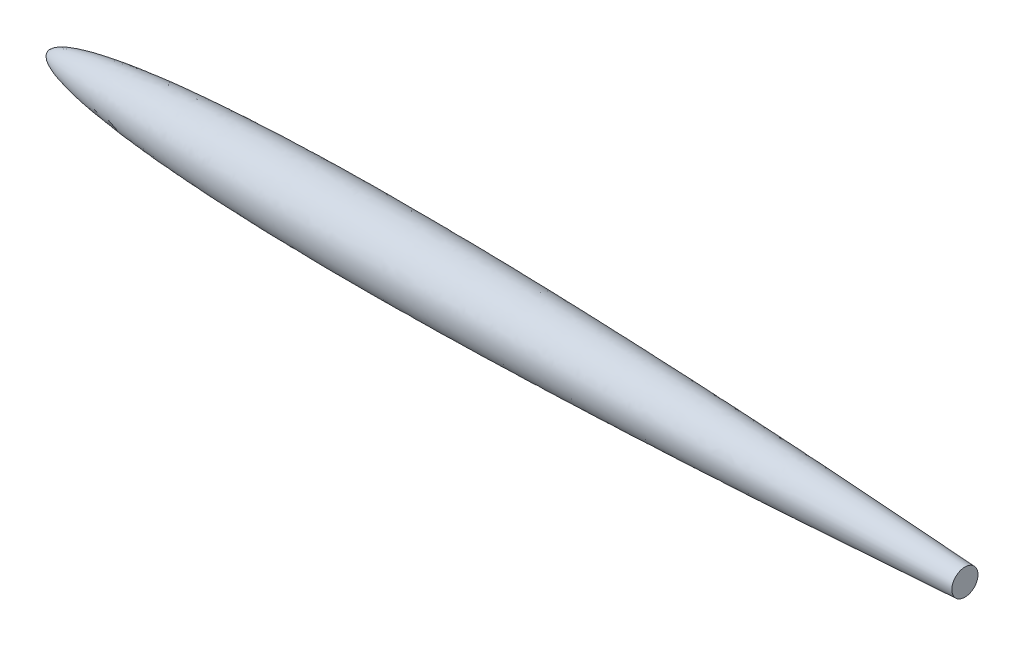
SolidWorks part; units mm, degrees
ref_plane "Front Plane" through (0, 0, 0) normal (0, 0, 1) x (1, 0, 0)
ref_plane "Top Plane" through (0, 0, 0) normal (0, 1, 0) x (1, 0, 0)
ref_plane "Right Plane" through (0, 0, 0) normal (1, 0, 0) x (0, 0, -1)
sketch "Sketch2" plane through (0, 0, 0) normal (0, 1, 0) x (1, 0, 0)
  line L0 (0, 0) -> (11000, 0)
  spline S0 degree 4 poles (0, 0) (0.0002, 1.4166) (0.1225, 4.2408) (0.6739, 8.4547) (2.1097, 13.9385) (4.13, 19.1147) (6.6109, 23.9643) (9.9914, 29.3681) (13.8074, 34.3715) (18.0051, 39.0824) (24.0066, 45.0125) (32.3839, 52.2354) (43.384, 60.1944) (57.0761, 68.6181) (73.983, 77.7243) (92.7893, 86.6435) (113.9578, 95.5167) (137.4556, 104.3111) (166.2995, 114.136) (201.291, 124.8338) (243.0702, 136.2047) (291.673, 147.964) (341.2433, 158.778) (390.608, 168.603) (439.7192, 177.609) (500.6517, 187.9807) (573.4692, 199.2826) (658.6122, 211.1866) (758.0842, 223.6079) (859.6848, 234.9957) (963.387, 245.4645) (1069.1706, 255.1028) (1175.0326, 263.8354) (1280.9578, 271.7615) (1386.9346, 278.9616) (1492.954, 285.5022) (1625.577, 292.9263) (1784.8272, 300.7239) (1970.7211, 308.3762) (2183.2661, 315.3874) (2395.8558, 320.8604) (2608.4762, 324.9557) (2821.1167, 327.8069) (3033.7692, 329.5269) (3299.5919, 330.3841) (3618.5808, 329.5138) (3990.7204, 326.0523) (4415.9852, 319.2091) (4841.2016, 309.8574) (5266.3634, 298.3074) (5691.4677, 284.8151) (6116.5132, 269.5907) (6541.4998, 252.8057) (6966.4276, 234.5973) (7391.2968, 215.0715) (7816.1072, 194.3061) (8187.764, 175.0965) (8506.2884, 157.9049) (8771.6988, 143.0951) (8984.0106, 130.9561) (9196.3055, 118.5234) (9382.048, 107.3844) (9541.2445, 97.6474) (9673.9002, 89.4049) (9780.02, 82.7331) (9912.6633, 74.2947) (10032.035, 66.5803) (10138.1364, 59.6277) (10230.971, 53.4713) (10284.0168, 49.9324) (10337.0641, 46.3721) (10390.1043, 42.7909) (10443.153, 39.1874) (10496.1834, 35.5635) (10549.2402, 31.9155) (10602.2495, 28.2488) (10655.3329, 24.5543) (10708.2897, 20.8463) (10761.4536, 17.1004) (10814.2582, 13.3575) (10861.0394, 10.0201) (10900.2084, 7.2123) (10934.3368, 4.7545) (10958.871, 2.9835) (10991.7181, 0.6028) (11015.0262, -1.0918) (11049.9588, -3.6388) (11071.8096, -5.2409) (11099.5819, -7.2784) (11124.1625, -9.0892) (11155.0411, -11.3693) (11188.9639, -13.8862) (11223.5859, -16.4645) (11266.4367, -19.6696) (11318.0968, -23.5545) (11369.6077, -27.4555) (11421.2086, -31.3904) (11472.7604, -35.3439) (11524.3346, -39.3212) (11584.4862, -43.9929) (11670.4236, -50.7243) (11756.3495, -57.532) (11842.2728, -64.4184) (11928.1873, -71.3847) (11996.9163, -77.0066) (12048.459, -81.2601) (12082.8201, -84.1126) (12100, -85.543) knots 0 0 0 0 0 0.000464 0.000929 0.001393 0.001858 0.002287 0.002716 0.003486 0.003922 0.004359 0.005488 0.007118 0.008378 0.009638 0.011797 0.013955 0.015919 0.017882 0.02181 0.025978 0.030146 0.034314 0.038482 0.042518 0.046554 0.054626 0.062698 0.07077 0.079497 0.088224 0.096952 0.105679 0.114406 0.123133 0.13186 0.140587 0.158059 0.17553 0.193002 0.210474 0.227946 0.245418 0.26289 0.280362 0.315306 0.35025 0.385194 0.420137 0.455081 0.490025 0.524969 0.559913 0.594857 0.6298 0.664744 0.699688 0.71716 0.734632 0.752104 0.769576 0.787048 0.795784 0.80452 0.813256 0.821992 0.839464 0.843832 0.8482 0.852567 0.856935 0.861303 0.865671 0.870039 0.874407 0.878775 0.883143 0.887511 0.891879 0.896247 0.900615 0.902799 0.904983 0.907167 0.909351 0.912184 0.915017 0.916433 0.91785 0.920682 0.923515 0.926348 0.929181 0.932013 0.937679 0.943345 0.946177 0.94901 0.954676 0.960341 0.966007 0.977338 0.983003 0.988669 0.994334 1 1 1 1 1 construction
  spline S1 degree 4 poles (0, 0) (0.0002, 1.4166) (0.1225, 4.2408) (0.6739, 8.4547) (2.1097, 13.9385) (4.13, 19.1147) (6.6109, 23.9643) (9.9914, 29.3681) (13.8074, 34.3715) (18.0051, 39.0824) (24.0066, 45.0125) (32.3839, 52.2354) (43.384, 60.1944) (57.0761, 68.6181) (73.983, 77.7243) (92.7893, 86.6435) (113.9578, 95.5167) (137.4556, 104.3111) (166.2995, 114.136) (201.291, 124.8338) (243.0702, 136.2047) (291.673, 147.964) (341.2433, 158.778) (390.608, 168.603) (439.7192, 177.609) (500.6517, 187.9807) (573.4692, 199.2826) (658.6122, 211.1866) (758.0842, 223.6079) (859.6848, 234.9957) (963.387, 245.4645) (1069.1706, 255.1028) (1175.0326, 263.8354) (1280.9578, 271.7615) (1386.9346, 278.9616) (1492.954, 285.5022) (1625.577, 292.9263) (1784.8272, 300.7239) (1970.7211, 308.3762) (2183.2661, 315.3874) (2395.8558, 320.8604) (2608.4762, 324.9557) (2821.1167, 327.8069) (3033.7692, 329.5269) (3299.5919, 330.3841) (3618.5808, 329.5138) (3990.7204, 326.0523) (4415.9852, 319.2091) (4841.2016, 309.8574) (5266.3634, 298.3074) (5691.4677, 284.8151) (6116.5132, 269.5907) (6541.4998, 252.8057) (6966.4276, 234.5973) (7391.2968, 215.0715) (7816.1072, 194.3061) (8187.764, 175.0965) (8506.2884, 157.9049) (8771.6988, 143.0951) (8984.0106, 130.9561) (9196.3055, 118.5234) (9382.048, 107.3844) (9541.2445, 97.6474) (9673.9002, 89.4049) (9780.02, 82.7331) (9912.6633, 74.2947) (10032.035, 66.5803) (10138.1364, 59.6277) (10230.971, 53.4713) (10284.0168, 49.9324) (10337.0641, 46.3721) (10390.1043, 42.7909) (10443.153, 39.1874) (10496.1834, 35.5635) (10549.2402, 31.9155) (10602.2495, 28.2488) (10655.3329, 24.5543) (10708.2897, 20.8463) (10761.4536, 17.1004) (10814.2582, 13.3575) (10861.0394, 10.0201) (10900.2084, 7.2123) (10934.3368, 4.7545) (10958.871, 2.9835) (10981.8033, 1.3214) (10993.9727, 0.438) (11000, 0) knots 0 0 0 0 0 0.000464 0.000929 0.001393 0.001858 0.002287 0.002716 0.003486 0.003922 0.004359 0.005488 0.007118 0.008378 0.009638 0.011797 0.013955 0.015919 0.017882 0.02181 0.025978 0.030146 0.034314 0.038482 0.042518 0.046554 0.054626 0.062698 0.07077 0.079497 0.088224 0.096952 0.105679 0.114406 0.123133 0.13186 0.140587 0.158059 0.17553 0.193002 0.210474 0.227946 0.245418 0.26289 0.280362 0.315306 0.35025 0.385194 0.420137 0.455081 0.490025 0.524969 0.559913 0.594857 0.6298 0.664744 0.699688 0.71716 0.734632 0.752104 0.769576 0.787048 0.795784 0.80452 0.813256 0.821992 0.839464 0.843832 0.8482 0.852567 0.856935 0.861303 0.865671 0.870039 0.874407 0.878775 0.883143 0.887511 0.891879 0.896247 0.900615 0.902799 0.904983 0.907167 0.909351 0.909351 0.909351 0.909351 0.909351
  point P2 (-3709.1353, 4608.2194)
  point P3 (-3718.027, 3745.7211)
ref_plane "Plane1" through (9020, 0, 0) normal (1, 0, 0) x (0, 0, -1)
sketch "Sketch3" plane through (9020, 0, 0) normal (1, 0, 0) x (0, 0, -1)
  circle A0 centre (0, 0) radius 660
  dimension "D1" = 1320
revolve "Revolve1" add sketch "Sketch2" angle 360 about L0
extrude "Cut-Extrude3" cut sketch "Sketch3" along normal blind 2750 contours A0
equation "\"chord\"= 11m'uncut chord length"
equation "\"maxThickness\" = 0.06'naca symmetric airfoil last two digits divided by 100"
equation "\"percutChord\"= 0.18'percent of the chord to cut from the tail end"
equation "\"D1@Plane1\"= ( 1 - \"percutChord\" ) * \"chord\""
equation "\"D1@Sketch3\"=2*\"chord\"*\"maxThickness\""
